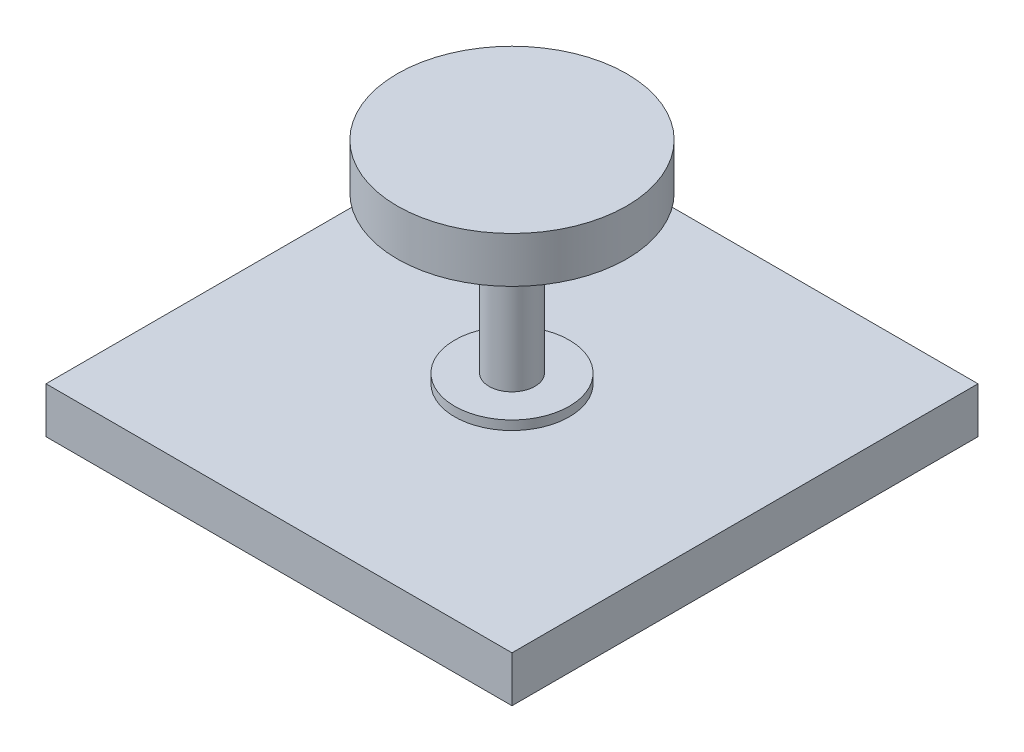
SolidWorks part; units mm, degrees
ref_plane "Front Plane" through (0, 0, 0) normal (0, 0, 1) x (1, 0, 0)
ref_plane "Top Plane" through (0, 0, 0) normal (0, 1, 0) x (1, 0, 0)
ref_plane "Right Plane" through (0, 0, 0) normal (1, 0, 0) x (0, 0, -1)
sketch "Sketch1" plane through (0, 0, 0) normal (0, 1, 0) x (1, 0, 0)
  line L1 (-50.8, -50.8) -> (50.8, -50.8)
  line L2 (-50.8, -50.8) -> (-50.8, 50.8)
  line L3 (-50.8, 50.8) -> (50.8, 50.8)
  line L4 (50.8, -50.8) -> (50.8, 50.8)
  line L5 (-50.8, -50.8) -> (50.8, 50.8) construction
  line L6 (-50.8, 50.8) -> (50.8, -50.8) construction
  point P0 (0, 0)
  dimension "D1" = 101.6
extrude "Boss-Extrude1" add sketch "Sketch1" along normal blind 10
sketch "Sketch2" plane through (0, 0, 0) normal (0, -1, 0) x (-1, 0, 0)
  circle A0 centre (0, 0) radius 5
  dimension "D1" = 10
extrude "Cut-Extrude1" cut sketch "Sketch2" against normal blind 5
sketch "Sketch3" plane through (0, 10, 0) normal (0, 1, 0) x (1, 0, 0)
  circle A0 centre (0, 0) radius 12.5
  dimension "D1" = 25
extrude "Boss-Extrude2" add sketch "Sketch3" along normal blind 2
sketch "Sketch4" plane through (0, 12, 0) normal (0, 1, 0) x (1, 0, 0)
  circle A0 centre (0, 0) radius 5
  dimension "D1" = 10
extrude "Boss-Extrude3" add sketch "Sketch4" along normal blind 34.0547
sketch "Sketch5" plane through (0, 46.0547, 0) normal (0, 1, 0) x (1, 0, 0)
  circle A0 centre (0, 0) radius 25
  dimension "D1" = 50
extrude "Boss-Extrude4" add sketch "Sketch5" along normal blind 10
